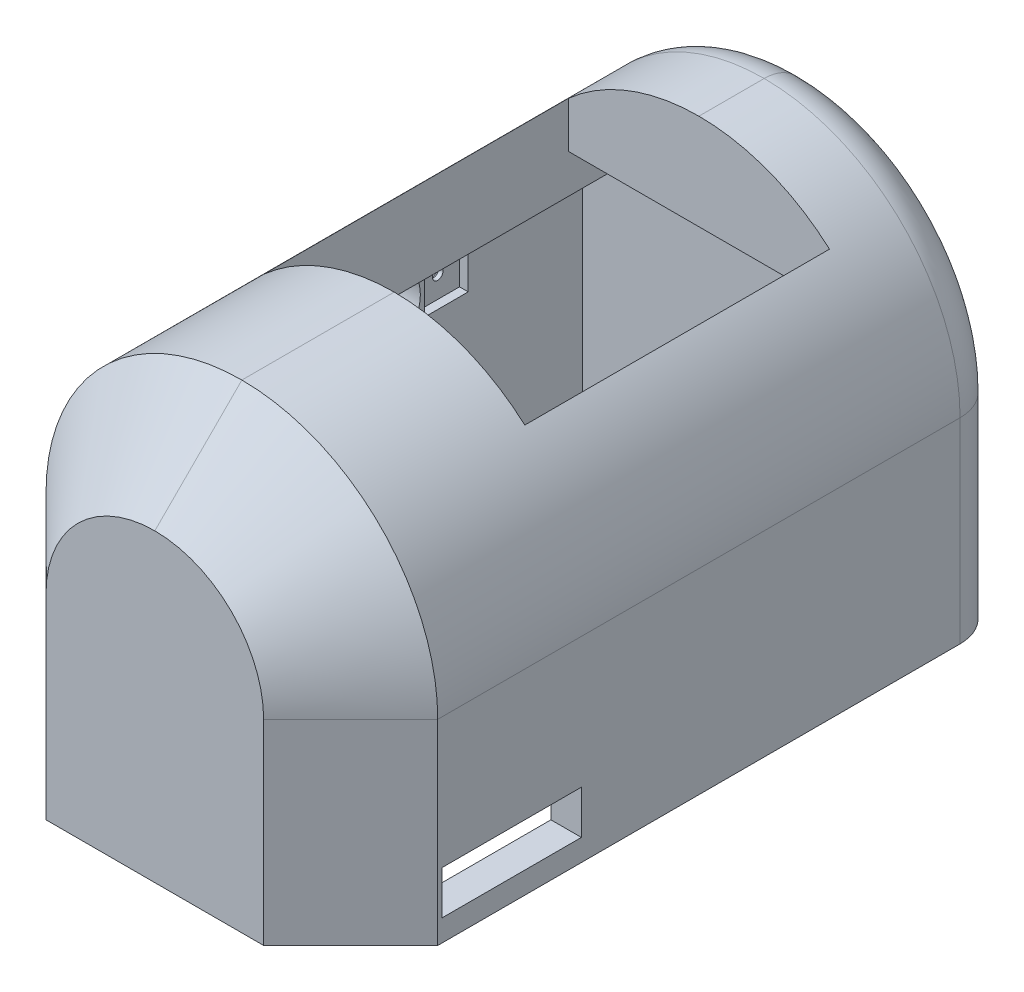
SolidWorks part; units mm, degrees
note: '?' marks a value the reader was unsure of.
ref_plane "Piano frontale" through (0, 0, 0) normal (0, 0, 1) x (1, 0, 0)
ref_plane "Piano superiore" through (0, 0, 0) normal (0, 1, 0) x (1, 0, 0)
ref_plane "Piano destro" through (0, 0, 0) normal (1, 0, 0) x (0, 0, -1)
sketch "Schizzo1" plane through (0, 0, 0) normal (0, 1, 0) x (1, 0, 0)
  line L1 (-45, -75) -> (45, -75)
  line L2 (-45, -75) -> (-45, 75)
  line L3 (-45, 75) -> (45, 75)
  line L4 (45, -75) -> (45, 75)
  line L5 (-45, -75) -> (45, 75) construction
  line L6 (-45, 75) -> (45, -75) construction
  point P0 (0, 0)
  dimension "D1" = 90
  dimension "D2" = 150
extrude "Estrusione-Estrusione1" add sketch "Schizzo1" along normal blind 90
sketch "Schizzo4" plane through (0, 90, 0) normal (0, 1, 0) x (1, 0, 0)
  line L1 (-30, -20) -> (30, -20)
  line L2 (-30, -20) -> (-30, 50)
  line L3 (-30, 50) -> (30, 50)
  line L4 (30, -20) -> (30, 50)
  point P0 (0, 0)
  dimension "D1" = 60
  dimension "D2" = 70
  dimension "D3" = 50
extrude "Taglio-Estrusione2" cut sketch "Schizzo4" against normal blind 90
fillet "Raccordo5" radius 45 1 edges at (-45, 90, 0)
fillet "Raccordo6" radius 45 1 edges at (45, 90, 0)
chamfer "Smusso2" distance 20 angle 45 4 edges at (45, 22.5, 75) (31.8198, 76.8198, 75) (-45, 22.5, 75) (-31.8198, 76.8198, 75)
sketch "Schizzo7" plane through (0, 0, 75) normal (0, 0, 1) x (1, 0, 0)
  line L0 (25, 0) -> (25, 45) construction
  line L1 (-25, 0) -> (25, 0)
  line L2 (-25, 0) -> (-25, 44.7532)
  line L3 (-25, 44.7532) -> (25, 44.7532)
  line L4 (25, 0) -> (25, 44.7532)
extrude "Estrusione-Estrusione2" add sketch "Schizzo7" along normal blind 50
chamfer "Smusso3" distance 20 angle 60 1 edges at (0, 44.7532, 125) first distance on face at (0, 44.7532, 100)
fillet "Raccordo7" radius 10 1 edges at (0, 44.7532, 105)
fillet "Raccordo8" radius 10 1 edges at (0, 10.1122, 125)
sketch "Schizzo9" plane through (0, 0, 0) normal (0, -1, 0) x (1, 0, 0)
  line L0 (-25, 75) -> (25, 75)
  line L1 (25, 75) -> (25, 125)
  line L2 (25, 125) -> (-25, 125)
  line L3 (-25, 125) -> (-25, 75)
extrude "Estrusione-Estrusione3" add sketch "Schizzo9" along normal blind 5
fillet "Raccordo9" radius 10 4 edges at (-45, 22.5, -75) (45, 22.5, -75) (31.8198, 76.8198, -75) (-31.8198, 76.8198, -75)
sketch "Schizzo13" plane through (0, 0, 20) normal (0, 0, -1) x (-1, 0, 0)
  line L0 (30, 0) -> (-30, 0) construction
  line L1 (-22.5, 0) -> (22.5, 0)
  line L2 (-22.5, 0) -> (-22.5, 38.416)
  line L3 (-22.5, 38.416) -> (22.5, 38.416)
  line L4 (22.5, 0) -> (22.5, 38.416)
  line L5 (-30, 0) -> (-30, 78.541) construction
  line L6 (30, 0) -> (30, 78.541) construction
  dimension "D1" = 7.5
  dimension "D2" = 7.5
extrude "Taglio-Estrusione3" cut sketch "Schizzo13" against normal blind 79.9783
sketch "Schizzo14" plane through (30, 0, 0) normal (-1, 0, 0) x (0, 0, 1)
  line L0 (-15, 78.541) -> (-15, 0) construction
  line L1 (20, 78.541) -> (-50, 78.541) construction
  line L2 (20, 0) -> (-50, 0) construction
  line L4 (-61.2099, 0) -> (56.6346, 0)
  line L5 (-61.2099, 0) -> (-61.2099, 59.041)
  line L6 (-61.2099, 59.041) -> (56.6346, 59.041)
  line L7 (56.6346, 0) -> (56.6346, 59.041)
extrude "Taglio-Estrusione4" cut sketch "Schizzo14" against normal blind 8
ref_axis "Assi1" through (0, 90, -65) along (0, 0, 1)?
ref_axis "Assi2" through (25, 44.7532, 75) along (-1, 0, 0)?
ref_plane "Piano1" through (0, 0, 0) normal (1, 0, 0) x (0, 0, -1)
mirror "Specchia1" about plane through (0, 0, 0) normal (1, 0, 0) of "Taglio-Estrusione4"
sketch "Schizzo16" plane through (0, 59.041, 0) normal (0, -1, 0) x (1, 0, 0)
  line L0 (30, -15) -> (38, -15) construction
  line L1 (30, 20) -> (30, -50) construction
  line L2 (38, 56.6346) -> (38, -61.2099) construction
  line L3 (34, -61.2099) -> (34, 49.6139) construction
  line L4 (38, -61.2099) -> (30, -61.2099) construction
  line L6 (30, -25) -> (34, -25)
  line L7 (30, -25) -> (30, -5)
  line L8 (30, -5) -> (34, -5)
  line L9 (34, -25) -> (34, -5)
  point P10 (34, -15)
  dimension "D1" = 20
sketch "Schizzo18" plane through (30, 0, 0) normal (-1, 0, 0) x (0, 0, 1)
  circle A0 centre (-15, 48.541) radius 5
  dimension "D1" = 10
extrude "Taglio-Estrusione5" cut sketch "Schizzo18" against normal blind 9
extrude "Taglio-Estrusione7" cut sketch "Schizzo16" against normal blind 2 contours L9 L8 L7 L6
sketch "Schizzo23" plane through (0, 0, 0) normal (0, -1, 0) x (1, 0, 0)
  line L1 (-38, -61.2099) -> (38, -61.2099)
  line L2 (-38, -61.2099) -> (-38, 56.6346)
  line L3 (-38, 56.6346) -> (38, 56.6346)
  line L4 (38, -61.2099) -> (38, 56.6346)
extrude "Taglio-Estrusione8" cut sketch "Schizzo23" against normal blind 38
hole_wizard "Foro per Vite M2-2" positions "Schizzo24" profile "Schizzo25" hole size "M2" standard "ISO"
sketch "Schizzo24" plane through (0, 0, 0) normal (0, -1, 0) x (-1, 0, 0)
  line L0 (0, 75) -> (0, -75) construction
  line L1 (-35, 75) -> (35, 75) construction
  line L2 (22.5, -75) -> (-22.5, -75) construction
  line L4 (0, 0) -> (53.8934, 0) construction
  line L5 (25, -75) -> (45, -55) construction
  line L6 (45, 65) -> (45, -55) construction
  line L8 (-45, -55) -> (-25, -75) construction
  line L9 (-45, -55) -> (-45, 65) construction
  point P0 (40, 67)
  point P2 (30, -61.5147)
  point P4 (-30, -61.5147)
  point P19 (-40, 67)
  point P33 (-41.5, 5)
  point P35 (41.5, 5)
  dimension "D1" = 40
  dimension "D2" = 40
  dimension "D3" = 8
  dimension "D4" = 8
  dimension "D5" = 6
  dimension "D6" = 15
  dimension "D7" = 6
  dimension "D8" = 15
  dimension "D9" = 3.5
  dimension "D10" = 3.5
  dimension "D11" = 70
  dimension "D12" = 70
sketch "Schizzo25" plane through (-40, 0, -67) normal (1, 0, 0) x (0, 0, -1)
  line L0 (0, 0) -> (0, 4)
  line L1 (0, 4) -> (1.2, 4)
  line L2 (1.2, 4) -> (1.2, 0)
  line L5 (1.2, 0) -> (0, 0)
  line L10 (0, 4) -> (-1.2, 4) construction
  line L11 (0, -6.35) -> (0, 107.95) construction
  dimension "Hole Dia." = 2.4
  dimension "Hole Depth" = 4
  dimension "Drill Angle" = 180
hole_wizard "Foro per Vite M4-1" positions "Schizzo3D1" profile "Schizzo26" hole size "M4" standard "ISO"
sketch3d "Schizzo3D1"
  line L0 (-25, -5, 125) -> (-25, -5, 75) construction
  line L3 (-22.5, 0, 99.9783) -> (-22.5, -16.7046, 99.9783) construction
  line L5 (-22.5, 0, 99.9783) -> (18.7748, 0, 99.9783) construction
  line L6 (22.5, 0, 99.9783) -> (-22.5, 0, 99.9783) construction
  point P0 (0, -5, 84.7796)
  dimension "D1" = 25
  dimension "D2" = 16
sketch "Schizzo26" plane through (0, -5, 84.7796) normal (1, 0, 0) x (0, 0, -1)
  line L0 (0, 0) -> (0, 10)
  line L1 (0, 10) -> (2.25, 10)
  line L2 (2.25, 10) -> (2.25, 0)
  line L5 (2.25, 0) -> (0, 0)
  line L10 (0, 10) -> (-2.25, 10) construction
  line L11 (0, -6.35) -> (0, 107.95) construction
  dimension "Hole Dia." = 4.5
  dimension "Hole Depth" = 10
  dimension "Drill Angle" = 180
sketch "Schizzo29" plane through (0, 38, 0) normal (0, -1, 0) x (1, 0, 0)
  line L1 (-30, -50) -> (30, -50)
  line L2 (-30, -50) -> (-30, -61.2099)
  line L3 (-30, -61.2099) -> (30, -61.2099)
  line L4 (30, -50) -> (30, -61.2099)
extrude "Taglio-Estrusione9" cut sketch "Schizzo29" against normal blind 30
sketch "Schizzo30" plane through (0, 0, -61.2099) normal (0, 0, 1) x (1, 0, 0)
  line L0 (38, 55.7788) -> (-32, 55.7788)
  line L1 (38, 59.041) -> (38, 0) construction
  line L2 (-32, 55.7788) -> (-32, 3.7788)
  line L3 (-32, 3.7788) -> (38, 3.7788)
  line L4 (38, 3.7788) -> (38, 55.7788)
  dimension "D1" = 70
  dimension "D2" = 52
extrude "Taglio-Estrusione10" [suppressed] cut sketch "Schizzo30" against normal blind 7
hole_wizard "Foro per Vite M2-3" [suppressed] positions "Schizzo31" profile "Schizzo32" hole size "M2" standard "ISO"
sketch "Schizzo31" [suppressed] plane through (0, 0, -68.2099) normal (0, 0, 1) x (1, 0, 0)
  point P0 (-29.5, 48.2788)
  point P2 (-29.5, 19.2788)
  point P4 (22.5, 6.2788)
  point P6 (22.5, 53.2788)
sketch "Schizzo32" plane through (-29.5, 48.2788, -68.2099) normal (1, 0, 0) x (0, -1, 0)
  line L0 (0, 0) -> (0, 4.721)
  line L1 (0, 4.721) -> (1.2, 4)
  line L2 (1.2, 4) -> (1.2, 0)
  line L5 (1.2, 0) -> (0, 0)
  line L10 (0, 4.721) -> (-1.2, 4) construction
  line L11 (0, -6.35) -> (0, 107.95) construction
  dimension "Hole Dia." = 2.4
  dimension "Hole Depth" = 4
  dimension "Drill Angle" = 118
sketch "Schizzo33" [suppressed] plane through (38, 0, 0) normal (-1, 0, 0) x (0, 0, 1)
  line L0 (-68.2099, 3.7788) -> (-68.2099, 55.7788) construction
  line L1 (-68.2099, 13.7788) -> (-64.2099, 13.7788)
  line L2 (-68.2099, 13.7788) -> (-68.2099, 23.7788)
  line L3 (-68.2099, 23.7788) -> (-64.2099, 23.7788)
  line L4 (-64.2099, 13.7788) -> (-64.2099, 23.7788)
  line L5 (-68.2099, 3.7788) -> (-61.2099, 3.7788) construction
  dimension "D1" = 10
  dimension "D2" = 4
  dimension "D3" = 10
extrude "Taglio-Estrusione11" [suppressed] cut sketch "Schizzo33" against normal blind 36 contours L4 L3 L2 L1
sketch "Schizzo36" plane through (0, 56.6546, 98.1287) normal (0, 0.5, 0.866) x (1, 0, 0)
  line L0 (0, -19.5161) -> (0, -51.0631) construction
  line L1 (25, -19.5161) -> (-25, -19.5161) construction
  line L2 (-25, -51.0631) -> (25, -51.0631) construction
  line L3 (-25, -35.2896) -> (25, -35.2896) construction
  line L4 (-25, -51.0631) -> (-25, -19.5161) construction
  line L5 (25, -19.5161) -> (25, -51.0631) construction
  line L7 (-23.0399, -21.1584) -> (23.0399, -21.1584)
  line L8 (-23.0399, -21.1584) -> (-23.0399, -49.4209)
  line L9 (-23.0399, -49.4209) -> (23.0399, -49.4209)
  line L10 (23.0399, -21.1584) -> (23.0399, -49.4209)
  line L11 (-23.0399, -21.1584) -> (23.0399, -49.4209) construction
  line L12 (-23.0399, -49.4209) -> (23.0399, -21.1584) construction
  point P12 (0, -35.2896)
extrude "Taglio-Estrusione12" cut sketch "Schizzo36" against normal blind 28
sketch "Schizzo37" plane through (23.0399, 0, 0) normal (-1, 0, 0) x (0, 0, 1)
  line L0 (122.8391, 13.8549) -> (108.7079, 38.331)
  line L1 (108.7079, 38.331) -> (106.8091, 37.2347)
  line L2 (84.4592, 24.331) -> (108.7079, 38.331) construction
  line L3 (106.8091, 37.2347) -> (120.9403, 12.7587)
  line L4 (98.5904, -0.1451) -> (122.8391, 13.8549) construction
  line L5 (120.9403, 12.7587) -> (122.8391, 13.8549)
extrude "Estrusione-Estrusione4" add sketch "Schizzo37" along normal up to next
sketch "Schizzo38" plane through (0, 56.6546, 98.1287) normal (0, 0.5, 0.866) x (1, 0, 0)
  line L0 (0, -19.5161) -> (0, -51.0631) construction
  line L3 (25, -19.5161) -> (-25, -19.5161) construction
  line L6 (-25, -51.0631) -> (25, -51.0631) construction
  line L7 (-25, -35.2896) -> (25, -35.2896) construction
  line L8 (-25, -51.0631) -> (-25, -19.5161) construction
  line L9 (25, -19.5161) -> (25, -51.0631) construction
  circle A0 centre (-12.5, -35.2896) radius 6
  circle A1 centre (12.5, -35.2896) radius 2.5
  dimension "D1" = 12
  dimension "D2" = 5
  dimension "D3" = 12.5
extrude "Taglio-Estrusione13" cut sketch "Schizzo38" against normal blind 28
ref_axis "Assi3" through (107.2361, 48.541, -15) along (-1, 0, 0)?
sketch "Schizzo39" plane through (-38, 0, 0) normal (1, 0, 0) x (0, 0, -1)
  line L0 (15, 57.9632) -> (15, 37.1322) construction
  line L2 (-5, 53.541) -> (5, 53.541)
  line L3 (-5, 53.541) -> (-5, 43.541)
  line L4 (-5, 43.541) -> (5, 43.541)
  line L5 (5, 53.541) -> (5, 43.541)
  line L6 (-5, 53.541) -> (5, 43.541) construction
  line L7 (-5, 43.541) -> (5, 53.541) construction
  line L8 (25, 53.541) -> (35, 53.541)
  line L9 (25, 53.541) -> (25, 43.541)
  line L10 (25, 43.541) -> (35, 43.541)
  line L11 (35, 53.541) -> (35, 43.541)
  line L12 (25, 53.541) -> (35, 43.541) construction
  line L13 (25, 43.541) -> (35, 53.541) construction
  circle A0 centre (15, 48.541) radius 9
  point P0 (15, 48.541)
  point P6 (0, 48.541)
  point P11 (30, 48.541)
  point P17 (0, 48.541)
  dimension "D1" = 18
  dimension "D2" = 15
  dimension "D3" = 10
  dimension "D4" = 10
  dimension "D5" = 10
  dimension "D6" = 10
extrude "Taglio-Estrusione14" cut sketch "Schizzo39" against normal blind 2
sketch "Schizzo40" plane through (-45, 0, 0) normal (-1, 0, 0) x (0, 0, 1)
  line L0 (-65, 0) -> (55, 0) construction
  line L1 (22, 15) -> (54, 15)
  line L2 (22, 15) -> (22, 5)
  line L3 (22, 5) -> (54, 5)
  line L4 (54, 15) -> (54, 5)
  line L5 (22, 15) -> (54, 5) construction
  line L6 (22, 5) -> (54, 15) construction
  line L7 (55, 0) -> (55, 45) construction
  point P0 (38, 10)
  dimension "D1" = 5
  dimension "D2" = 10
  dimension "D3" = 32
  dimension "D4" = 1
extrude "Taglio-Estrusione15" cut sketch "Schizzo40" against normal blind 10 contours L3 L4 L1 L2
sketch "Schizzo42" plane through (-45, 0, 0) normal (-1, 0, 0) x (0, 0, 1)
  circle A0 centre (-30, 48.541) radius 4
  circle A1 centre (0, 48.541) radius 4
  point P0 (-15, 48.541)
  dimension "D3" = 8
  dimension "D4" = 8
  dimension "D1" = 15
  dimension "D2" = 15
extrude "Taglio-Estrusione16" cut sketch "Schizzo42" against normal blind 3 contours A1 | A0
hole_wizard "Foro svasato per Vite M2-3" positions "Schizzo47" profile "Schizzo48" countersink size "M2" standard "ISO"
sketch "Schizzo47" plane through (-42, 0, 0) normal (-1, 0, 0) x (0, 0, 1)
  point P0 (-30, 48.541)
  point P3 (0, 48.541)
sketch "Schizzo48" plane through (-42, 48.541, -30) normal (0, 1, 0) x (0, 0, 1)
  line L0 (0, 0) -> (0, 6.721)
  line L1 (0, 6.721) -> (1.2, 6)
  line L2 (1.2, 6) -> (1.2, 1)
  line L3 (1.2, 1) -> (2.2, 0)
  line L5 (2.2, 0) -> (0, 0)
  line L6 (-1.2, 1) -> (-2.2, 0) construction
  line L10 (0, 6.721) -> (-1.2, 6) construction
  line L11 (0, -6.35) -> (0, 107.95) construction
  dimension "Hole Dia." = 2.4
  dimension "Hole Depth" = 6
  dimension "Near C'Sink Dia." = 4.4
  dimension "Near C'Sink Angle" = 90
  dimension "Drill Angle" = 118
sketch "Schizzo50" [suppressed] plane through (0, 0, -61.2099) normal (0, 0, 1) x (1, 0, 0)
  line L0 (38, 59.041) -> (38, 55.7788)
  line L1 (38, 55.7788) -> (-32, 55.7788)
  line L2 (-32, 55.7788) -> (-32, 3.7788)
  line L3 (-32, 3.7788) -> (-35.1813, 3.7788)
  line L4 (-35.1813, 3.7788) -> (-35.1813, 59.041)
  line L5 (-38, 59.041) -> (-30, 59.041) construction
  line L6 (-35.1813, 59.041) -> (38, 59.041)
extrude "Taglio-Estrusione18" [suppressed] cut sketch "Schizzo50" against normal blind 7
sketch "Schizzo53" plane through (-40, 0, 0) normal (1, 0, 0) x (0, 0, -1)
  circle A0 centre (15, 48.541) radius 9
  point P0 (15, 48.541)
extrude "Taglio-Estrusione19" cut sketch "Schizzo53" against normal blind 2.75
sketch "Schizzo54" plane through (0, 38, 0) normal (0, -1, 0) x (1, 0, 0)
  line L1 (30, 20) -> (-30, 20)
  line L2 (30, 20) -> (30, 56.6346)
  line L3 (30, 56.6346) -> (-30, 56.6346)
  line L4 (-30, 20) -> (-30, 56.6346)
extrude "Taglio-Estrusione20" cut sketch "Schizzo54" against normal blind 24.75
sketch "Schizzo55" plane through (0, 44.7532, 0) normal (0, 1, 0) x (1, 0, 0)
  line L1 (-25, -75) -> (25, -75)
  line L2 (-25, -75) -> (-25, -144.1984)
  line L3 (-25, -144.1984) -> (25, -144.1984)
  line L4 (25, -75) -> (25, -144.1984)
extrude "Taglio-Estrusione21" cut sketch "Schizzo55" against normal blind 66
sketch "Schizzo57" plane through (-22.5, 0, 0) normal (1, 0, 0) x (0, 0, -1)
  line L0 (-75, 38.416) -> (-56.6346, 38.416) construction
  line L1 (-56.6346, 0) -> (-75, 0)
  line L2 (-56.6346, 0) -> (-56.6346, 38.416)
  line L3 (-56.6346, 38.416) -> (-75, 38.416)
  line L4 (-75, 0) -> (-75, 38.416)
extrude "Estrusione-Estrusione5" add sketch "Schizzo57" along normal blind 47
mirror "Specchia2" about plane through (0, 0, 0) normal (1, 0, 0) of "Taglio-Estrusione15"
sketch "Schizzo58" plane through (0, 15, 0) normal (0, -1, 0) x (1, 0, 0)
  line L1 (-45, 22) -> (-38, 22)
  line L2 (-45, 22) -> (-45, 54)
  line L3 (-45, 54) -> (-38, 54)
  line L4 (-38, 22) -> (-38, 54)
extrude "Estrusione-Estrusione6" add sketch "Schizzo58" along normal blind 11
